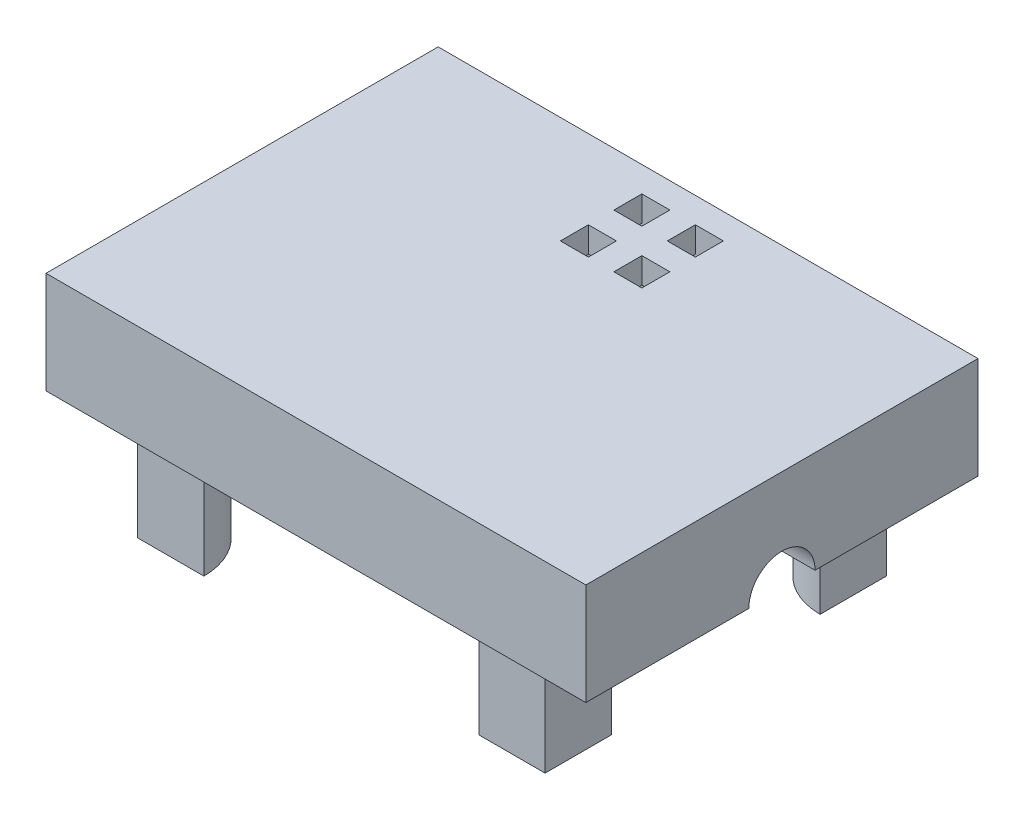
SolidWorks part; units mm, degrees
ref_plane "Alzado" through (0, 0, 0) normal (0, 0, 1) x (1, 0, 0)
ref_plane "Planta" through (0, 0, 0) normal (0, 1, 0) x (1, 0, 0)
ref_plane "Vista lateral" through (0, 0, 0) normal (1, 0, 0) x (0, 0, -1)
sketch "Croquis1" plane through (0, 0, 0) normal (0, 1, 0) x (1, 0, 0)
  line L0 (0, 0) -> (0, 13.4) construction
  line L1 (-16, -13.4) -> (16, -13.4)
  line L2 (-16, -13.4) -> (-16, 13.4)
  line L3 (-16, 13.4) -> (16, 13.4)
  line L4 (16, -13.4) -> (16, 13.4)
  line L5 (-16, -13.4) -> (16, 13.4) construction
  line L6 (-16, 13.4) -> (16, -13.4) construction
  line L7 (-21.2, -15.4) -> (21.2, -15.4)
  line L8 (-21.2, -15.4) -> (-21.2, 15.4)
  line L9 (-21.2, 15.4) -> (21.2, 15.4)
  line L10 (21.2, -15.4) -> (21.2, 15.4)
  line L11 (-21.2, -15.4) -> (21.2, 15.4) construction
  line L12 (-21.2, 15.4) -> (21.2, -15.4) construction
  line L13 (-1, 13.4) -> (1, 13.4) construction
  line L14 (-1, 11.2) -> (-1, 9.2) construction
  line L15 (1, 13.4) -> (3.2, 13.4)
  line L16 (1, 13.4) -> (1, 11.2)
  line L17 (1, 11.2) -> (3.2, 11.2)
  line L18 (3.2, 13.4) -> (3.2, 11.2)
  line L19 (-1, 13.4) -> (-3.2, 13.4)
  line L20 (-1, 13.4) -> (-1, 11.2)
  line L21 (-1, 11.2) -> (-3.2, 11.2)
  line L22 (-3.2, 13.4) -> (-3.2, 11.2)
  line L23 (-1, 9.2) -> (-3.2, 9.2)
  line L24 (-1, 9.2) -> (-1, 7)
  line L25 (-1, 7) -> (-3.2, 7)
  line L26 (-3.2, 9.2) -> (-3.2, 7)
  line L27 (1, 9.2) -> (3.2, 9.2)
  line L28 (1, 9.2) -> (1, 7)
  line L29 (1, 7) -> (3.2, 7)
  line L30 (3.2, 9.2) -> (3.2, 7)
  line L31 (-1, 9.2) -> (1, 9.2) construction
  line L32 (1, 11.2) -> (1, 9.2) construction
  line L33 (-1, 11.2) -> (1, 11.2) construction
  arc A0 (-16, 8.2) -> (-10.8, 13.4) centre (-16, 13.4) ccw
  arc A1 (-16, -8.2) -> (-10.8, -13.4) centre (-16, -13.4) cw
  arc A2 (10.8, -13.4) -> (16, -8.2) centre (16, -13.4) cw
  arc A3 (16, 8.2) -> (10.8, 13.4) centre (16, 13.4) cw
  point P0 (0, 0)
  point P6 (0, 0)
  point P24 (0, 13.4)
  dimension "D5" = 5.2
  dimension "D1" = 5.2
  dimension "D2" = 2
  dimension "D3" = 32
  dimension "D4" = 26.8
  dimension "D6" = 2
  dimension "D7" = 6.4
  dimension "D8" = 2
  dimension "D9" = 6.4
extrude "Saliente-Extruir1" add sketch "Croquis1" against normal blind 6 contours L7 L10 L9 L8 L4 L1 L2 L3 region at (-20.6759, 0, 0)
extrude "Saliente-Extruir2" add sketch "Croquis1<3>" against normal blind 14.4 contours L2 A0 L3 | A1 L2 L1 | A3 L4 L3 | A2 L1 L4 region at (-13.7931, 0, 11.1931) region at (13.7931, 0, 11.1931) region at (-13.7931, 0, -11.1931) region at (13.7931, 0, -11.1931)
sketch "Croquis1<3>" plane through (0, 0, 0) normal (0, 1, 0) x (1, 0, 0) same geometry as "Croquis1"
extrude "Saliente-Extruir3" add sketch "Croquis1<4>" along normal blind 2 contours L4 A3 L3 L18 L17 L16 L20 L21 L22 A0 L2 A1 L1 A2 L26 L23 L24 L25 L27 L30 L29 L28 | L2 A0 L3 | A3 L4 L3 | A2 L1 L4 | A1 L2 L1 | L7 L10 L9 L8 L4 L1 L2 L3 region at (-13.7931, 0, 11.1931) region at (0, 0, 0.2621) region at (13.7931, 0, 11.1931) region at (-13.7931, 0, -11.1931) region at (13.7931, 0, -11.1931) region at (-20.6759, 0, 0)
sketch "Croquis1<4>" plane through (0, 0, 0) normal (0, 1, 0) x (1, 0, 0) same geometry as "Croquis1"
ref_plane "Plano1" through (21.2, 0, 0) normal (1, 0, 0) x (0, 0, -1)
sketch "Croquis2" plane through (21.2, 0, 0) normal (1, 0, 0) x (0, 0, -1)
  line L0 (-15.4, -6) -> (15.4, -6) construction
  line L1 (-2.6, -6) -> (2.6, -6)
  arc A0 (-2.6, -6) -> (2.6, -6) centre (0, -6) cw
  dimension "D1" = 2.6
extrude "Cortar-Extruir1" cut sketch "Croquis2" against normal up to surface (42.4 mm away) up to face at (-21.2, -2, 0)
